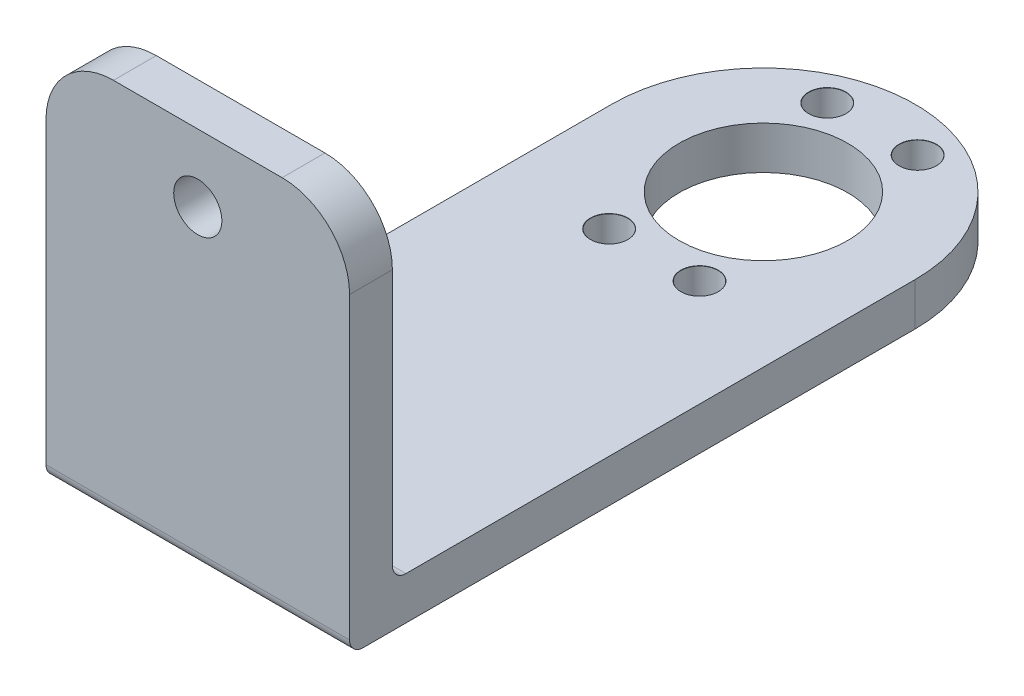
SolidWorks part; units mm, degrees
material "ABS PC"
ref_plane "Front Plane" through (0, 0, 0) normal (0, 0, 1) x (1, 0, 0)
ref_plane "Top Plane" through (0, 0, 0) normal (0, 1, 0) x (1, 0, 0)
ref_plane "Right Plane" through (0, 0, 0) normal (1, 0, 0) x (0, 0, -1)
sketch "Sketch1" plane through (0, 0, 0) normal (0, 1, 0) x (1, 0, 0)
  line L5 (-22.5, -77.5) -> (22.5, -77.5)
  line L6 (-22.5, -77.5) -> (-22.5, 0)
  line L8 (22.5, -77.5) -> (22.5, 0)
  line L9 (-22.5, -77.5) -> (22.5, 0) construction
  line L10 (-22.5, 0) -> (22.5, -77.5) construction
  arc A0 (22.5, 0) -> (-22.5, 0) centre (0, 0) ccw
  point P2 (0, -38.75)
  dimension "D1" = 45
  dimension "D2" = 100
  dimension "D3" = 45
extrude "Boss-Extrude1" add sketch "Sketch1" along normal blind 6.35
sketch "Sketch2" plane through (0, 6.35, 0) normal (0, 1, 0) x (1, 0, 0)
  line L0 (-6.697, 16.1679) -> (6.697, 16.1679) construction
  circle A0 centre (0, 0) radius 17.5 construction
  circle A1 centre (0, 0) radius 17.5 construction
  circle A2 centre (0, 0) radius 17.5 construction
  circle A3 centre (0, 0) radius 17.5 construction
  circle A4 centre (0, 0) radius 17.5 construction
  circle A5 centre (0, 0) radius 17.5 construction
  circle A6 centre (0, 0) radius 17.5 construction
  circle A7 centre (0, 0) radius 17.5 construction
  point P3 (-6.697, 16.1679)
  point P5 (-16.1679, -6.697)
  point P7 (6.697, 16.1679)
  point P9 (16.1679, 6.697)
  point P11 (16.1679, -6.697)
  point P13 (6.697, -16.1679)
  point P15 (-6.697, -16.1679)
  point P16 (0, 0)
  point P18 (-16.1679, 6.697)
  dimension "D1" = 35
  dimension "D2" = 8
hole_wizard "M5 Clearance Hole1" positions "Sketch3" profile "Sketch4" hole size "M5" standard "ANSI Metric" end condition through all
sketch "Sketch3" plane through (0, 6.35, 0) normal (0, 1, 0) x (1, 0, 0)
  point P0 (-6.697, -16.1679)
  point P3 (6.697, -16.1679)
  point P6 (6.697, 16.1679)
  point P15 (-6.697, 16.1679)
sketch "Sketch4" plane through (-6.697, 6.35, 16.1679) normal (1, 0, 0) x (0, 0, 1)
  line L0 (0, 0) -> (0, 6.35)
  line L1 (0, 6.35) -> (2.75, 6.35)
  line L2 (2.75, 6.35) -> (2.75, 0.025)
  line L3 (2.75, 0.025) -> (2.775, 0)
  line L5 (2.775, 0) -> (0, 0)
  line L6 (-2.75, 0.025) -> (-2.775, 0) construction
  line L11 (0, -6.35) -> (0, 107.95) construction
  dimension "Thru Hole Dia." = 5.5
  dimension "Thru Hole Depth" = 6.35
  dimension "Near C'Sink Dia." = 5.55
  dimension "Near C'Sink Angle" = 90
sketch "Sketch5" plane through (0, 6.35, 0) normal (0, 1, 0) x (1, 0, 0)
  circle A0 centre (0, 0) radius 12.5
  dimension "D1" = 25
extrude "Cut-Extrude1" cut sketch "Sketch5" against normal through all
sketch "Sketch6" [suppressed] plane through (0, 6.35, 0) normal (0, 1, 0) x (1, 0, 0)
  line L0 (-22.5, -77.5) -> (22.5, -77.5) construction
  circle A0 centre (0, -71) radius 3.3782
  dimension "D1" = 6.7564
  dimension "D2" = 6.5
sketch "Sketch7" [suppressed] plane through (0, 6.35, 0) normal (0, 1, 0) x (1, 0, 0)
  line L0 (12.5, -58.5) -> (-12.5, -58.5) construction
  line L1 (12.5, -63) -> (-12.5, -63)
  line L2 (12.5, -54) -> (-12.5, -54)
  line L3 (0, -71) -> (0, 0) construction
  line L4 (12.5, -42.5) -> (-12.5, -42.5) construction
  line L5 (12.5, -47) -> (-12.5, -47)
  line L6 (12.5, -38) -> (-12.5, -38)
  line L7 (12.5, -26.5) -> (-12.5, -26.5) construction
  line L8 (12.5, -31) -> (-12.5, -31)
  line L9 (12.5, -22) -> (-12.5, -22)
  arc A0 (12.5, -63) -> (12.5, -54) centre (12.5, -58.5) ccw
  arc A1 (-12.5, -54) -> (-12.5, -63) centre (-12.5, -58.5) ccw
  arc A2 (12.5, -47) -> (12.5, -38) centre (12.5, -42.5) ccw
  arc A3 (-12.5, -38) -> (-12.5, -47) centre (-12.5, -42.5) ccw
  arc A4 (12.5, -31) -> (12.5, -22) centre (12.5, -26.5) ccw
  arc A5 (-12.5, -22) -> (-12.5, -31) centre (-12.5, -26.5) ccw
  circle A6 centre (0, -71) radius 3.3782 construction
  point P2 (0, -58.5)
  point P15 (0, -42.5)
  point P22 (0, -26.5)
  point P28 (0, -63)
  dimension "D2" = 4.5
  dimension "D4" = 8
  dimension "D3" = 25
  dimension "D1" = 3
extrude "Cut-Extrude3" [suppressed] cut sketch "Sketch7" against normal through all
sketch "Sketch12" plane through (0, 0, 77.5) normal (0, 0, 1) x (1, 0, 0)
  line L0 (-22.5, 6.35) -> (22.5, 6.35) construction
  line L1 (22.5, 0) -> (-22.5, 0)
  line L2 (22.5, 0) -> (22.5, 56.35)
  line L3 (22.5, 56.35) -> (-22.5, 56.35)
  line L4 (-22.5, 0) -> (-22.5, 56.35)
  point P5 (0, 0)
  dimension "D1" = 50
extrude "Boss-Extrude2" add sketch "Sketch12" along normal blind 6.35
sketch "Sketch13" plane through (0, 0, 77.5) normal (0, 0, -1) x (-1, 0, 0)
  line L0 (22.5, 6.35) -> (-22.5, 6.35) construction
  point P0 (0, 46.35)
  dimension "D1" = 40
hole_wizard "1/4 Clearance Hole1" positions "Sketch16" profile "Sketch17" hole size "1/4" standard "ANSI Inch" end condition through all
sketch "Sketch16" plane through (0, 0, 77.5) normal (0, 0, -1) x (-1, 0, 0)
  point P0 (0, 46.35)
sketch "Sketch17" plane through (0, 46.35, 77.5) normal (1, 0, 0) x (0, 1, 0)
  line L0 (0, 0) -> (0, 6.35)
  line L1 (0, 6.35) -> (3.5712, 6.35)
  line L2 (3.5712, 6.35) -> (3.5712, 0.635)
  line L3 (3.5712, 0.635) -> (4.2062, 0)
  line L5 (4.2062, 0) -> (0, 0)
  line L6 (-3.5712, 0.635) -> (-4.2062, 0) construction
  line L11 (0, -6.35) -> (0, 107.95) construction
  dimension "Thru Hole Dia." = 7.1425
  dimension "Thru Hole Depth" = 6.35
  dimension "Near C'Sink Dia." = 8.4125
  dimension "Near C'Sink Angle" = 90
fillet "Fillet1" radius 10 2 edges at (-22.5, 56.35, 80.675) (22.5, 56.35, 80.675)
fillet "Fillet2" radius 2 2 edges at (0, 0, 83.85) (0, 6.35, 77.5)
